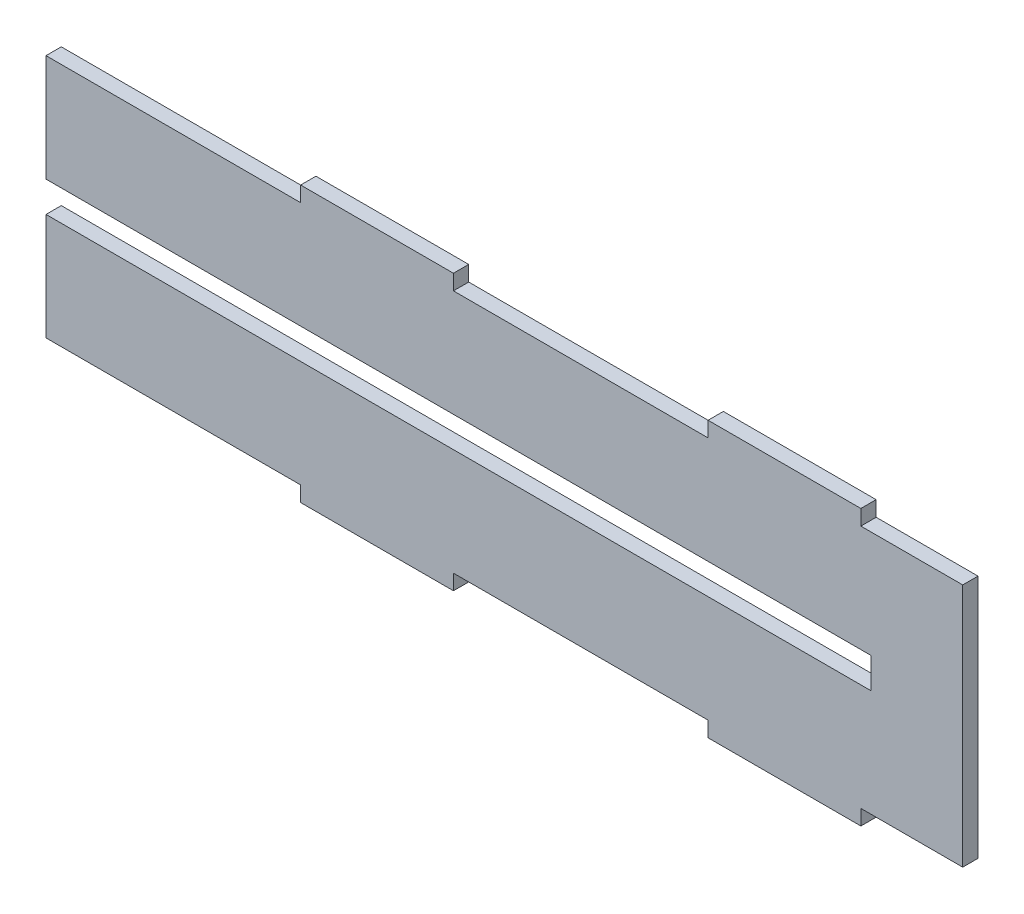
SolidWorks part; units mm, degrees
ref_plane "Plano frontal" through (0, 0, 0) normal (0, 0, 1) x (1, 0, 0)
ref_plane "Plano superior" through (0, 0, 0) normal (0, 1, 0) x (1, 0, 0)
ref_plane "Plano direito" through (0, 0, 0) normal (1, 0, 0) x (0, 0, -1)
sketch "Esboço1" plane through (0, 0, 0) normal (0, 0, 1) x (1, 0, 0)
  line L0 (0, -48) -> (50, -48)
  line L1 (0, 0) -> (50, 0)
  line L2 (0, 0) -> (0, -48)
  line L3 (50, -51) -> (80, -51)
  line L5 (50, -48) -> (50, -51)
  line L6 (80, -51) -> (80, -48)
  line L7 (80, -48) -> (130, -48)
  line L8 (130, -48) -> (130, -51)
  line L9 (160, -51) -> (160, -48)
  line L10 (160, -48) -> (180, -48)
  line L11 (130, -51) -> (160, -51)
  line L12 (0, -24) -> (180, -24) construction
  line L13 (0, 0) -> (50, 0)
  line L14 (80, 0) -> (130, 0)
  line L15 (160, 0) -> (180, 0)
  line L16 (160, 3) -> (160, 0)
  line L17 (130, 3) -> (160, 3)
  line L18 (130, 0) -> (130, 3)
  line L19 (80, 3) -> (80, 0)
  line L20 (50, 3) -> (80, 3)
  line L21 (50, 0) -> (50, 3)
  line L22 (80, 0) -> (130, 0)
  line L23 (160, 0) -> (180, 0)
  line L24 (180, 0) -> (180, -48)
  line L25 (0, -21) -> (162, -21)
  line L26 (0, -21) -> (0, -27)
  line L27 (0, -27) -> (162, -27)
  line L28 (162, -21) -> (162, -27)
  point P27 (0, -24)
  dimension "D2" = 48
  dimension "D3" = 50
  dimension "D4" = 3
  dimension "D5" = 30
  dimension "D6" = 50
  dimension "D7" = 3
  dimension "D8" = 30
  dimension "D9" = 3
  dimension "D10" = 180
  dimension "D11" = 162
  dimension "D12" = 6
  dimension "D14" = 30
extrude "Ressalto-extrusão1" add sketch "Esboço1" along normal blind 3 contours L12 L2 L0 L5 L3 L6 L7 L8 L11 L9 L10 | L2 L12 L15 L16 L17 L18 L14 L19 L20 L21 L1 region at (1.8793, -37.5, 0)
